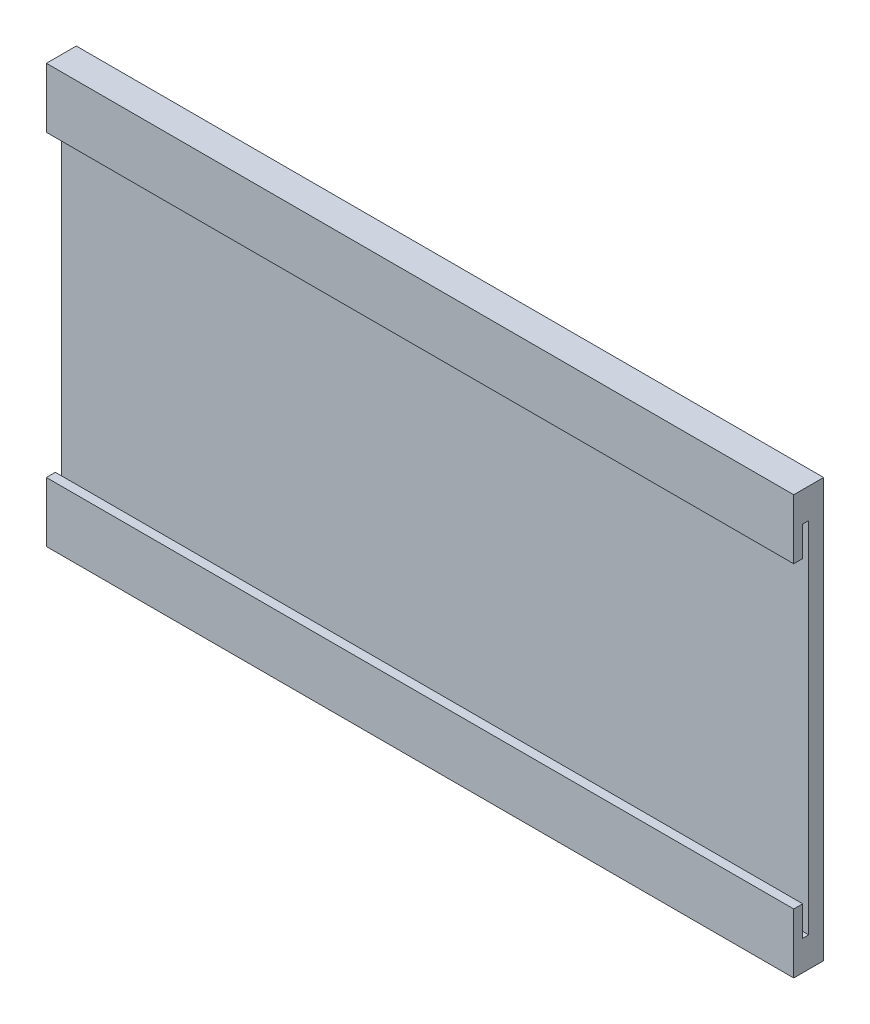
SolidWorks part; units mm, degrees
ref_plane "Front Plane" through (0, 0, 0) normal (0, 0, 1) x (1, 0, 0)
ref_plane "Top Plane" through (0, 0, 0) normal (0, 1, 0) x (1, 0, 0)
ref_plane "Right Plane" through (0, 0, 0) normal (1, 0, 0) x (0, 0, -1)
sketch "Sketch1" plane through (0, 0, 0) normal (0, 0, 1) x (1, 0, 0)
  line L0 (0, 60) -> (250, 60)
  line L1 (0, 70) -> (250, 70)
  line L2 (0, 70) -> (0, -70)
  line L3 (0, -70) -> (250, -70)
  line L4 (250, 70) -> (250, -70)
  line L5 (0, 50) -> (250, 50)
  line L6 (0, -60) -> (250, -60)
  line L7 (0, -50) -> (250, -50)
  line L8 (0, 0) -> (250, 0) construction
  line L9 (0, 0) -> (250, 0) construction
  dimension "D1" = 140
  dimension "D3" = 20
  dimension "D4" = 10
  dimension "D5" = 20
  dimension "D6" = 10
extrude "Boss-Extrude1" add sketch "Sketch1" along normal blind 5 and the other way blind 5 contours L2 L5 L4 L0 | L4 L1 L2 L0 | L7 L2 L6 L4 | L6 L2 L3 L4 | L2 L7 L4 L5 | L2 L1 L4 L3 region at (125, 65, 0) region at (125, 55, 0) region at (125, 0, 0) region at (125, -55, 0) region at (125, -65, 0)
extrude "Cut-Extrude1" cut sketch "Sketch1<3>" along normal through all contours L2 L7 L4 L5 | L2 L9 L4 L5 region at (125, 25, 0) region at (125, -25, 0)
sketch "Sketch1<3>" plane through (0, 0, 0) normal (0, 0, 1) x (1, 0, 0) same geometry as "Sketch1"
extrude "Cut-Extrude2" cut sketch "Sketch1<4>" along normal blind 2 contours L2 L5 L4 L0 | L7 L2 L6 L4 region at (125, 55, 0) region at (125, -55, 0)
sketch "Sketch1<4>" plane through (0, 0, 0) normal (0, 0, 1) x (1, 0, 0) same geometry as "Sketch1"
